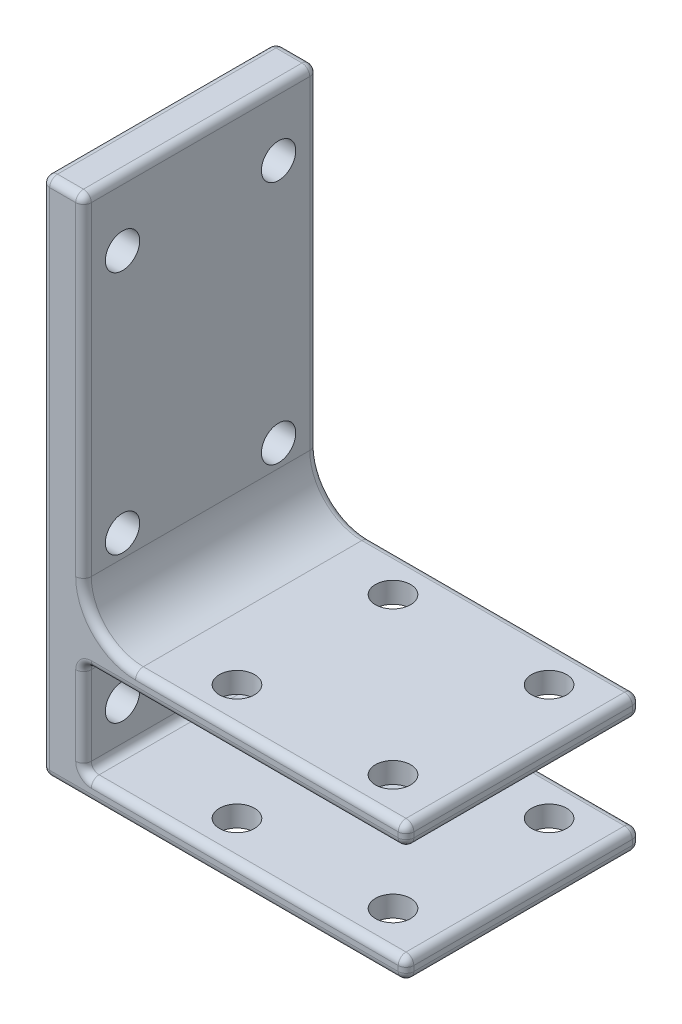
SolidWorks part; units mm, degrees
material "Nylon 6/10"
ref_plane "Front Plane" through (0, 0, 0) normal (0, 0, 1) x (1, 0, 0)
ref_plane "Top Plane" through (0, 0, 0) normal (0, 1, 0) x (1, 0, 0)
ref_plane "Right Plane" through (0, 0, 0) normal (1, 0, 0) x (0, 0, -1)
sketch "Sketch1" plane through (0, 0, 0) normal (0, 0, 1) x (1, 0, 0)
  line L0 (0, 0) -> (0, 100)
  line L1 (0, 100) -> (8, 100)
  line L2 (8, 100) -> (8, 4)
  line L3 (8, 4) -> (70, 4)
  line L4 (70, 4) -> (70, 0)
  line L5 (70, 0) -> (0, 0)
  dimension "D1" = 4
  dimension "D2" = 70
  dimension "D3" = 8
  dimension "D4" = 100
extrude "base" add sketch "Sketch1" along normal blind 45
sketch "Sketch2" plane through (8, 0, 0) normal (1, 0, 0) x (0, 0, -1)
  line L0 (-45, 4) -> (-45, 100) construction
  line L1 (-45, 26.25) -> (0, 26.25)
  line L2 (-45, 26.25) -> (-45, 22.25)
  line L3 (-45, 22.25) -> (0, 22.25)
  line L4 (0, 26.25) -> (0, 22.25)
  line L5 (0, 4) -> (0, 100) construction
  line L6 (-45, 4) -> (0, 4) construction
  dimension "D1" = 4
  dimension "D2" = 18.25
extrude "top skin" add sketch "Sketch2" along normal up to surface (62 mm away) up to face at (70, 2, 22.5)
hole_wizard "slider bolt hole pattern" positions "Sketch3" profile "Sketch4" hole size "M6" standard "ANSI Metric" end condition through all
sketch "Sketch3" plane through (8, 0, 0) normal (1, 0, 0) x (0, 0, -1)
  line L1 (-37.5, 87.5) -> (-7.5, 87.5)
  line L2 (-37.5, 87.5) -> (-37.5, 12.5)
  line L3 (-37.5, 12.5) -> (-7.5, 12.5)
  line L4 (-7.5, 87.5) -> (-7.5, 12.5)
  line L5 (-22.5, 12.5) -> (-22.5, 0) construction
  line L6 (-45, 0) -> (0, 0) construction
  line L8 (-22.5, 87.5) -> (-22.5, 100) construction
  line L9 (-45, 100) -> (0, 100) construction
  point P0 (-37.5, 87.5)
  point P1 (-7.5, 12.5)
  point P60 (-37.5, 12.5)
  point P61 (-7.5, 87.5)
  point P87 (-37.5, 40.5)
  point P89 (-7.5, 40.5)
  dimension "D1" = 75
  dimension "D2" = 30
  dimension "D3" = 28
sketch "Sketch4" plane through (8, 87.5, 37.5) normal (0, 1, 0) x (0, 0, -1)
  line L0 (0, 0) -> (0, 8)
  line L1 (0, 8) -> (3.3, 8)
  line L2 (3.3, 8) -> (3.3, 0)
  line L5 (3.3, 0) -> (0, 0)
  line L11 (0, -6.35) -> (0, 107.95) construction
  dimension "Thru Hole Dia." = 6.6
  dimension "Thru Hole Depth" = 8
hole_wizard "desktop bolt hole pattern" positions "Sketch5" profile "Sketch6" hole size "1/4" standard "ANSI Inch" end condition through all
sketch "Sketch5" plane through (0, 26.25, 0) normal (0, 1, 0) x (1, 0, 0)
  line L1 (30, -7.5) -> (60, -7.5)
  line L2 (30, -7.5) -> (30, -37.5)
  line L3 (30, -37.5) -> (60, -37.5)
  line L4 (60, -7.5) -> (60, -37.5)
  line L5 (60, -22.5) -> (70, -22.5)
  line L6 (70, -45) -> (70, 0) construction
  point P1 (30, -7.5)
  point P2 (60, -37.5)
  point P97 (30, -37.5)
  point P98 (60, -7.5)
  dimension "D2" = 30
  dimension "D1" = 10
  dimension "D3" = 30
sketch "Sketch6" plane through (30, 26.25, 7.5) normal (1, 0, 0) x (0, 0, 1)
  line L0 (0, 0) -> (0, 26.25)
  line L1 (0, 26.25) -> (3.3782, 26.25)
  line L2 (3.3782, 26.25) -> (3.3782, 0)
  line L5 (3.3782, 0) -> (0, 0)
  line L11 (0, -6.35) -> (0, 107.95) construction
  dimension "Thru Hole Dia." = 6.7564
  dimension "Thru Hole Depth" = 26.25
fillet "visible corner fillet" radius 10 1 edges at (8, 26.25, 22.5)
fillet "break other corners" radius 1.5 31 edges at (70, 0, 22.5) (70, 4, 22.5) (70, 26.25, 22.5) (70, 22.25, 22.5) (70, 2, 0) (39, 4, 0) (8, 13.125, 0) (39, 22.25, 0) (70, 24.25, 0) (44, 26.25, 0) (10.9289, 29.1789, 0) (8, 68.125, 0) (4, 100, 0) (35, 0, 0) (0, 100, 22.5) (0, 0, 22.5) (0, 50, 0) (0, 50, 45) (4, 100, 45) (8, 68.125, 45) (10.9289, 29.1789, 45) (44, 26.25, 45) (70, 24.25, 45) (39, 22.25, 45) (8, 13.125, 45) (39, 4, 45) (70, 2, 45) (35, 0, 45) (8, 4, 22.5) (8, 22.25, 22.5) (8, 100, 22.5)
equation "\"board_thickness\"= 18mm"
equation "\"way_width\"= 75mm"
equation "\"way_thickness\"= 50mm"
equation "\"radial_clearance\"= 0.1mm"
equation "\"slider_width\"= \"way_width\"-2* \"radial_clearance\""
equation "\"slider_thickness\"= \"way_thickness\" - 2 * \"radial_clearance\""
equation "\"column_width\"= \"way_width\" + 2 * \"board_thickness\""
equation "\"boxway_slot_width\"= 50mm"
equation "\"keeper_rail_width\"= (\"column_width\" - \"boxway_slot_width\")/2"
equation "\"slider_length\"= 125mm"
equation "\"nut_diameter\"= 22mm"
equation "\"nut_length\"= 15mm"
equation "\"leadscrew_diameter\"= 10mm"
equation "\"leadscrew_radial_clearance\"= 1mm"
equation "\"bearing_bolt_pattern_width\"= 30mm"
equation "\"bearing_bolt_pattern_height\"= 75mm"
equation "\"desktop_bolt_pattern_width\"= 30mm"
equation "\"desktop_bolt_pattern_height\"= 30mm"
equation "\"bearing_bolt_nut_counterbore_diameter\"= 12mm"
equation "\"bearing_bolt_nut_counterbore_depth\"= 10mm"
equation "\"desktop_depth\"= 500mm"
equation "\"desktop_width\"= 650mm"
equation "\"desktop_thickness\"= 18mm"
equation "\"leg_height\"=100mm"
equation "\"leg_width\"=18mm"
equation "\"leg_length\"=500mm"
equation "\"lap_joint_height\"= 50mm"
equation "\"lap_dowel_diameter\"= 8mm"
equation "\"lap_dowel_hole_z_spacing\"=30"
equation "\"skin_thicknes\"= 4"
equation "\"D1@Sketch1\"=\"skin_thicknes\""
equation "\"D1@Sketch2\"=\"skin_thicknes\""
equation "\"D2@Sketch2\"=\"desktop_thickness\" + 0.25"
equation "\"D1@Sketch3\"=\"bearing_bolt_pattern_height\""
equation "\"D2@Sketch3\"=\"bearing_bolt_pattern_width\""
equation "\"D2@Sketch5\"=\"desktop_bolt_pattern_width\""
equation "\"D3@Sketch5\"=\"desktop_bolt_pattern_height\""
